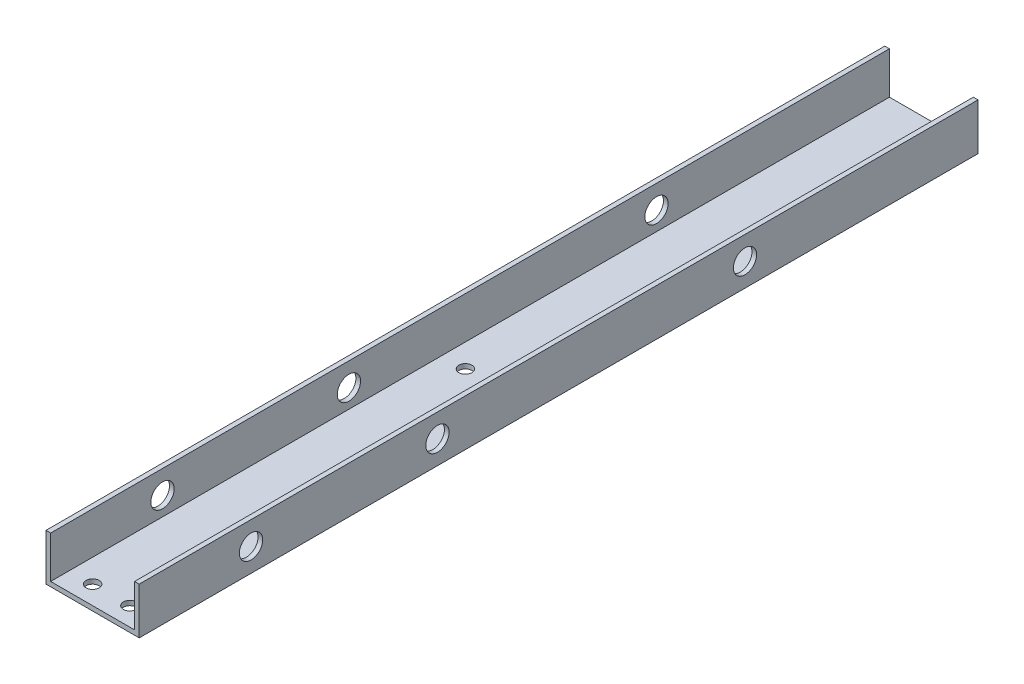
SolidWorks part; units mm, degrees
ref_plane "Front" through (0, 0, 0) normal (0, 0, 1) x (1, 0, 0)
ref_plane "Top" through (0, 0, 0) normal (0, 1, 0) x (1, 0, 0)
ref_plane "Right" through (0, 0, 0) normal (1, 0, 0) x (0, 0, -1)
sketch "Sketch1" plane through (0, 0, 0) normal (0, 0, 1) x (1, 0, 0)
  line L0 (48.26, 2.54) -> (48.26, 25.4)
  line L1 (0, 0) -> (50.8, 0)
  line L2 (0, 0) -> (0, 25.4)
  line L4 (50.8, 0) -> (50.8, 25.4)
  line L5 (2.54, 2.54) -> (48.26, 2.54)
  line L6 (2.54, 2.54) -> (2.54, 25.4)
  line L7 (50.8, 25.4) -> (48.26, 25.4)
  line L8 (0, 25.4) -> (2.54, 25.4)
  dimension "D1" = 25.4
  dimension "D2" = 50.8
  dimension "D3" = 2.54
extrude "Boss-Extrude1" add sketch "Sketch1" along normal blind 457.2
sketch "Sketch2" plane through (0, 0, 0) normal (0, -1, 0) x (1, 0, 0)
  line L0 (25.4, 457.2) -> (25.4, 437.2063) construction
  line L3 (0, 447.04) -> (15.24, 447.04) construction
  line L4 (15.24, 457.2) -> (15.24, 447.04) construction
  line L5 (0, 457.2) -> (50.8, 457.2) construction
  line L6 (0, 457.2) -> (0, 0) construction
  circle A1 centre (15.24, 447.04) radius 3.556
  circle A2 centre (35.56, 447.04) radius 3.556
  point P11 (0, 0)
  point P14 (0, 0)
  dimension "D1" = 10.16
  dimension "D2" = 15.24
extrude "Cut-Extrude1" cut sketch "Sketch2" against normal up to next
sketch "Sketch3" plane through (0, 0, 0) normal (0, -1, 0) x (1, 0, 0)
  line L0 (15.24, 447.04) -> (15.24, 243.84) construction
  line L1 (15.24, 447.04) -> (35.56, 447.04) construction
  line L2 (35.56, 447.04) -> (35.56, 243.84) construction
  line L3 (35.56, 243.84) -> (15.24, 243.84) construction
  circle A0 centre (15.24, 243.84) radius 3.556
  circle A1 centre (35.56, 243.84) radius 3.556
  circle A2 centre (15.24, 447.04) radius 3.556 construction
  dimension "D1" = 203.2
extrude "Cut-Extrude2" cut sketch "Sketch3" against normal up to next
sketch "Sketch4" plane through (0, 0, 0) normal (-1, 0, 0) x (0, 0, 1)
  line L0 (457.2, 12.7) -> (396.24, 12.7) construction
  line L1 (457.2, 25.4) -> (457.2, 0) construction
  line L2 (396.24, 12.7) -> (294.64, 12.7) construction
  line L4 (0, 12.7) -> (127, 12.7) construction
  line L5 (0, 25.4) -> (0, 0) construction
  circle A0 centre (396.24, 12.7) radius 6.35
  circle A1 centre (294.64, 12.7) radius 6.35
  circle A2 centre (127, 12.7) radius 6.35
  dimension "D2" = 12.7
  dimension "D4" = 127
  dimension "D1" = 60.96
  dimension "D3" = 101.6
extrude "Cut-Extrude3" cut sketch "Sketch4" against normal through all
